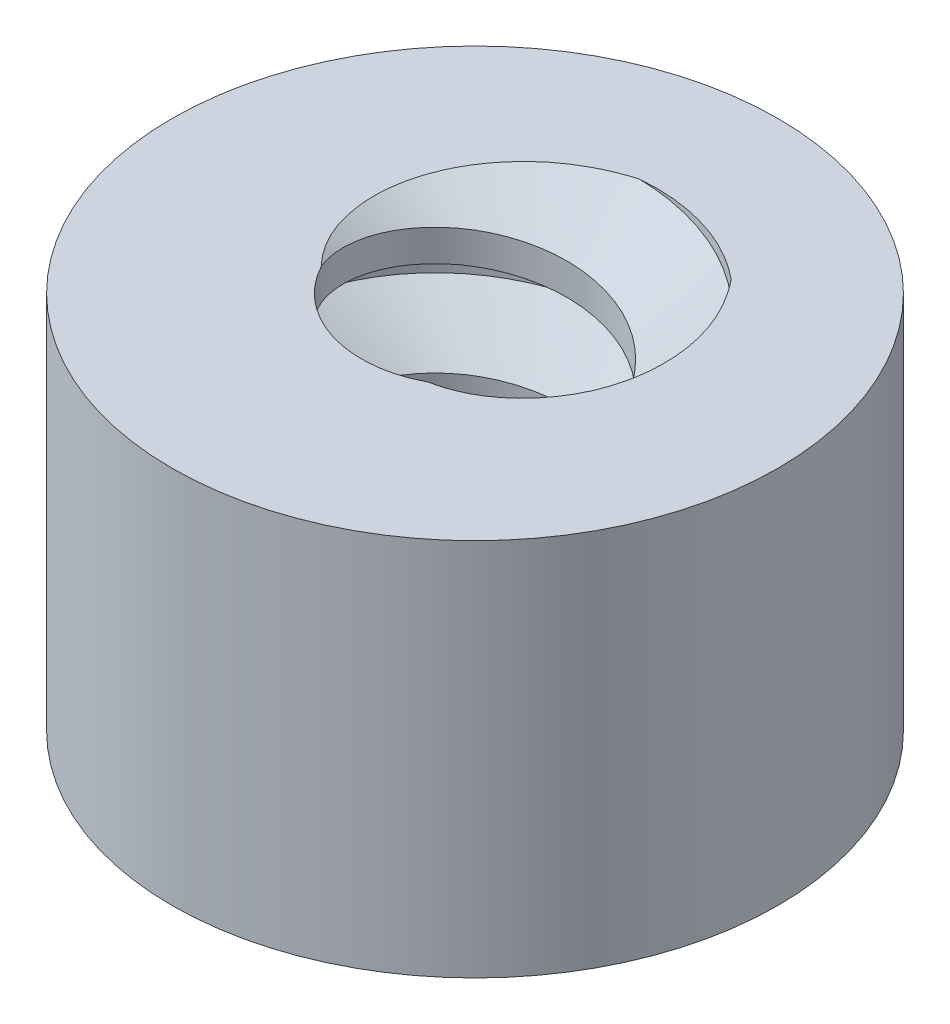
SolidWorks part; units mm, degrees
ref_plane "Front Plane" through (0, 0, 0) normal (0, 0, 1) x (1, 0, 0)
ref_plane "Top Plane" through (0, 0, 0) normal (0, 1, 0) x (1, 0, 0)
ref_plane "Right Plane" through (0, 0, 0) normal (1, 0, 0) x (0, 0, -1)
sketch "Sketch1" plane through (0, 0, 0) normal (0, 1, 0) x (1, 0, 0)
  circle A0 centre (0, 0) radius 5.08
  dimension "D1" = 10.16
extrude "Boss-Extrude1" add sketch "Sketch1" along normal blind 6.35
sketch "Sketch2" plane through (0, 6.35, 0) normal (0, 1, 0) x (1, 0, 0)
  circle A0 centre (0, 0) radius 1.905
  dimension "D1" = 3.81
extrude "Cut-Extrude1" cut sketch "Sketch2" against normal through all
thread "Thread1" pitch 2.1167 method cut profile "Thread Profile1" start angle 0, offset 3.54, length 12.54, pitch 2.1167, diameter 3.81
ref_plane "Plane1" through (-1.905, 9.89, 0) normal (0, 0, 1) x (-1, 0, 0)
sketch "Thread Profile1" plane through (-1.905, 9.89, 0) normal (0, 0, 1) x (-1, 0, 0)
  line L0 (0, 0) -> (0, 2.1167) construction
  line L1 (0, 0) -> (1.1457, 0.6615)
  line L2 (1.1457, 0.6615) -> (1.1457, 0.926)
  line L3 (1.1457, 0.926) -> (0, 1.5875)
  line L4 (1.1457, 0.7937) -> (0, 0.7937) construction
  line L11 (0, 0) -> (0, 1.5875)
  point P2 (0, 0)
  dimension "Pitch" = 2.1167
  dimension "Profile_Angle" = 60
  dimension "Profile_Land" = 0.2646
  dimension "Profile_Height" = 1.1457
